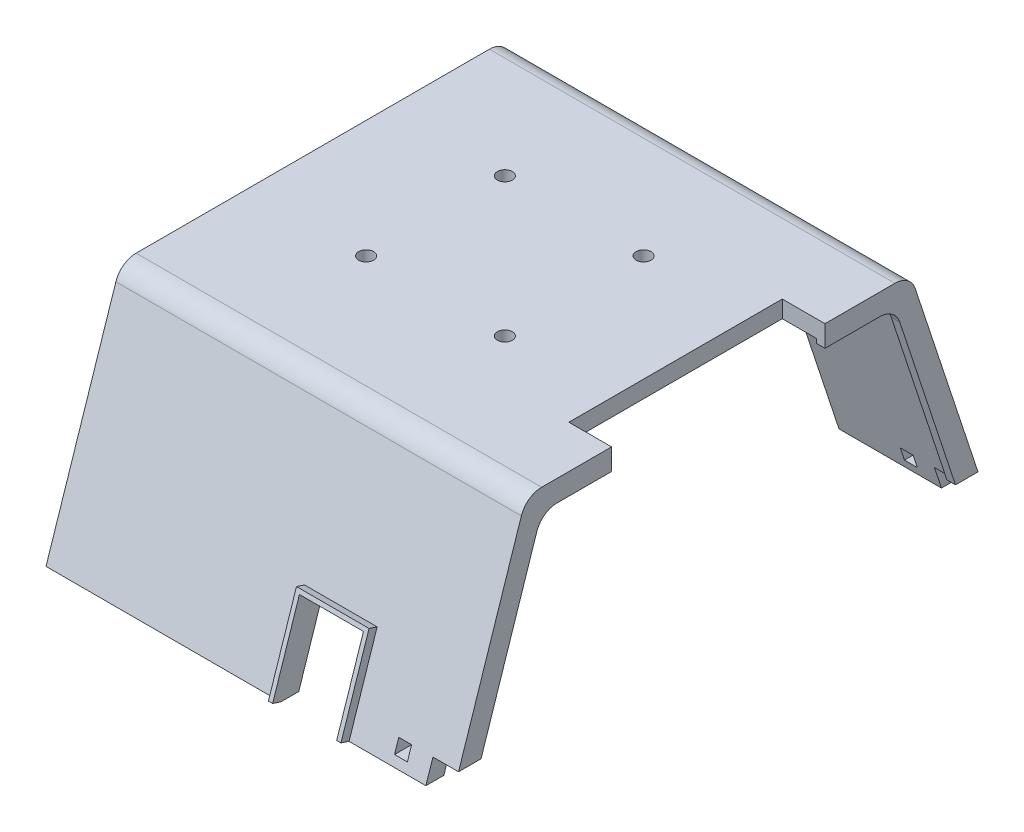
SolidWorks part; units mm, degrees
ref_plane "前视基准面" through (0, 0, 0) normal (0, 0, 1) x (1, 0, 0)
ref_plane "上视基准面" through (0, 0, 0) normal (0, 1, 0) x (1, 0, 0)
ref_plane "右视基准面" through (0, 0, 0) normal (1, 0, 0) x (0, 0, -1)
sketch "草图1" plane through (0, 0, 0) normal (1, 0, 0) x (0, 0, -1)
  line L0 (-62.5, 0) -> (-45, 53)
  line L1 (52.25, 0) -> (-52.25, 0) construction
  line L2 (-45, 53) -> (45, 53)
  line L3 (45, 53) -> (62.5, 0)
  line L4 (62.5, 0) -> (-62.5, 0)
  line L5 (0, 29.15) -> (0, -29.15) construction
  point P4 (0, 53)
  dimension "D1" = 125
  dimension "D2" = 90
  dimension "D3" = 53
extrude "凸台-拉伸1" add sketch "草图1" along normal blind 95
sketch "草图3" plane through (95, 0, 0) normal (1, 0, 0) x (0, 0, -1)
  line L0 (-60.8491, 5) -> (-47.5, 5)
  line L1 (-45, 53) -> (-62.5, 0) construction
  line L2 (-47.5, 5) -> (-47.5, 0)
  line L3 (52.25, 0) -> (-52.25, 0) construction
  line L4 (-47.5, 0) -> (-62.5, 0)
  line L5 (-62.5, 0) -> (-60.8491, 5)
  line L6 (62.5, 0) -> (60.8491, 5)
  line L7 (62.5, 0) -> (45, 53) construction
  line L8 (60.8491, 5) -> (47.5, 5)
  line L9 (47.5, 5) -> (47.5, 0)
  line L10 (47.5, 0) -> (62.5, 0)
  dimension "D1" = 5
  dimension "D2" = 15
  dimension "D3" = 15
  dimension "D4" = 5
extrude "凸台-拉伸3" add sketch "草图3" along normal blind 20
sketch "草图4" plane through (0, 0, 0) normal (0, 0, 1) x (1, 0, 0)
  line L1 (101.5, 3) -> (108.5, 3)
  line L2 (101.5, 3) -> (101.5, 0)
  line L3 (101.5, 0) -> (108.5, 0)
  line L4 (108.5, 3) -> (108.5, 0)
  line L5 (115, 0) -> (0, 0) construction
  line L6 (115, 5) -> (115, 0) construction
  dimension "D1" = 7
  dimension "D2" = 3
  dimension "D3" = 6.5
extrude "切除-拉伸1" cut sketch "草图4" against normal through all and the other way through all
sketch "草图5" plane through (0, 0, 0) normal (0, -1, 0) x (1, 0, 0)
  line L0 (99, -59) -> (99, -51) construction
  line L1 (97.5, -59) -> (97.5, -51)
  line L2 (100.5, -59) -> (100.5, -51)
  line L3 (111, -59) -> (111, -51) construction
  line L4 (109.5, -59) -> (109.5, -51)
  line L5 (112.5, -59) -> (112.5, -51)
  line L6 (99, 51) -> (99, 59) construction
  line L7 (97.5, 51) -> (97.5, 59)
  line L8 (100.5, 51) -> (100.5, 59)
  line L9 (111, 51) -> (111, 59) construction
  line L10 (109.5, 51) -> (109.5, 59)
  line L11 (112.5, 51) -> (112.5, 59)
  line L12 (101.5, -62.5) -> (101.5, -47.5) construction
  line L13 (101.5, -62.5) -> (0, -62.5) construction
  line L14 (115, -62.5) -> (108.5, -62.5) construction
  line L16 (101.5, 47.5) -> (95, 47.5) construction
  line L17 (115, 47.5) -> (108.5, 47.5) construction
  arc A0 (97.5, -59) -> (100.5, -59) centre (99, -59) ccw
  arc A1 (100.5, -51) -> (97.5, -51) centre (99, -51) ccw
  arc A2 (109.5, -59) -> (112.5, -59) centre (111, -59) ccw
  arc A3 (112.5, -51) -> (109.5, -51) centre (111, -51) ccw
  arc A4 (97.5, 51) -> (100.5, 51) centre (99, 51) ccw
  arc A5 (100.5, 59) -> (97.5, 59) centre (99, 59) ccw
  arc A6 (109.5, 51) -> (112.5, 51) centre (111, 51) ccw
  arc A7 (112.5, 59) -> (109.5, 59) centre (111, 59) ccw
  point P2 (99, -55)
  point P7 (111, -55)
  point P14 (99, 55)
  point P21 (111, 55)
  dimension "D1" = 3
  dimension "D2" = 3
  dimension "D3" = 3
  dimension "D4" = 3
  dimension "D5" = 12
  dimension "D6" = 2.5
  dimension "D7" = 7.5
  dimension "D8" = 7.5
  dimension "D9" = 8
  dimension "D10" = 8
  dimension "D11" = 8
  dimension "D12" = 8
  dimension "D13" = 12
  dimension "D14" = 7.5
  dimension "D15" = 7.5
extrude "切除-拉伸2" cut sketch "草图5" against normal through all
shell "抽壳1" thickness 2 removed face at (99, 0, 55)
sketch "草图6" plane through (95, 0, 0) normal (1, 0, 0) x (0, 0, -1)
  line L0 (-37.7709, 48) -> (37.7709, 48)
  line L1 (42.5187, 44.5677) -> (55.5835, 5)
  line L2 (60.8491, 5) -> (47.5, 5) construction
  line L3 (-42.5187, 44.5677) -> (-55.5835, 5)
  line L4 (-47.5, 5) -> (-60.8491, 5) construction
  line L5 (-47.5, 5) -> (-60.8491, 5) construction
  line L6 (-45, 53) -> (-60.8491, 5) construction
  line L7 (60.8491, 5) -> (45, 53) construction
  line L8 (45, 53) -> (-45, 53) construction
  line L9 (-55.5835, 5) -> (-47.5, 5)
  line L10 (-47.5, 5) -> (-47.5, 0)
  line L11 (52.25, 0) -> (-52.25, 0) construction
  line L12 (-47.5, 0) -> (-47.5, 5) construction
  line L13 (47.5, 5) -> (55.5835, 5)
  line L14 (47.5, 5) -> (47.5, 0)
  line L15 (47.5, 5) -> (47.5, 0) construction
  line L16 (-47.5, 0) -> (47.5, 0)
  arc A2 (37.7709, 48) -> (42.5187, 44.5677) centre (37.7709, 43) cw
  arc A3 (-37.7709, 48) -> (-42.5187, 44.5677) centre (-37.7709, 43) ccw
  point P30 (55.5835, 5)
  point P33 (-55.5835, 5)
  dimension "D5" = 5
  dimension "D1" = 5
  dimension "D2" = 5
  dimension "D3" = 5
extrude "切除-拉伸3" cut sketch "草图6" against normal blind 3
sketch "草图7" plane through (0, 53, 0) normal (0, 1, 0) x (1, 0, 0)
  line L0 (95, -25) -> (85, -25)
  line L1 (95, 45) -> (95, -45) construction
  line L2 (85, -25) -> (85, 25)
  line L3 (85, 25) -> (95, 25)
  line L4 (95, -25) -> (95, 25)
  line L6 (27.5, -15) -> (60, -15) construction
  line L7 (27.5, -15) -> (27.5, 17.5) construction
  line L8 (27.5, 17.5) -> (60, 17.5) construction
  line L9 (60, -15) -> (60, 17.5) construction
  line L11 (-29.15, 0) -> (29.15, 0) construction
  circle A0 centre (60, -15) radius 1.75
  circle A1 centre (60, 17.5) radius 1.75
  circle A2 centre (27.5, 17.5) radius 1.75
  circle A3 centre (27.5, -15) radius 1.75
  dimension "D6" = 3.5
  dimension "D7" = 3.5
  dimension "D8" = 3.5
  dimension "D9" = 3.5
  dimension "D1" = 10
  dimension "D2" = 25
  dimension "D3" = 25
  dimension "D4" = 32.5
  dimension "D5" = 32.5
  dimension "D10" = 15
  dimension "D11" = 35
extrude "切除-拉伸4" cut sketch "草图7" against normal through all
sketch "草图9" plane through (0, 18.6081, 56.3558) normal (0, 0.3135, 0.9496) x (1, 0, 0)
  line L0 (55, -19.5962) -> (55, 0.4038)
  line L1 (101.5, -19.5962) -> (0, -19.5962) construction
  line L2 (55, 0.4038) -> (70, 0.4038)
  line L3 (70, 0.4038) -> (70, -19.5962)
  line L4 (70, -19.5962) -> (55, -19.5962)
  line L5 (115, -14.3307) -> (115, -19.5962) construction
  dimension "D1" = 60
  dimension "D2" = 15
  dimension "D3" = 20
extrude "切除-拉伸5" cut sketch "草图9" against normal blind 3 contours L3 L2 L0 L4 region at (62.5, 9.4958, 59.3646)
sketch "草图10" plane through (0, 18.6081, 56.3558) normal (0, 0.3135, 0.9496) x (1, 0, 0)
  line L12 (55, -19.5962) -> (54, -19.5962)
  line L13 (55, -19.5962) -> (0, -19.5962) construction
  line L14 (54, -19.5962) -> (54, 1.4038)
  line L15 (54, 1.4038) -> (71, 1.4038)
  line L16 (71, 1.4038) -> (71, -19.5962)
  line L17 (101.5, -19.5962) -> (70, -19.5962) construction
  line L18 (71, -19.5962) -> (70, -19.5962)
  line L19 (70, -19.5962) -> (70, 0.4038)
  line L20 (70, 0.4038) -> (55, 0.4038)
  line L21 (55, 0.4038) -> (55, -19.5962)
  dimension "D1" = 1
  dimension "D2" = 1
  dimension "D3" = 1
extrude "凸台-拉伸4" add sketch "草图10" along normal blind 2
ref_plane "基准面1" through (0, 0, -80) normal (0, 0, 1) x (1, 0, 0)
sketch "草图11" plane through (0, 18.6081, -56.3558) normal (0, 0.3135, -0.9496) x (-1, 0, 0)
  line L0 (-67, -19.5962) -> (-67, 10.4038)
  line L1 (-101.5, -19.5962) -> (0, -19.5962) construction
  line L2 (-67, 10.4038) -> (-23, 10.4038)
  line L3 (-23, 10.4038) -> (-23, -19.5962)
  line L4 (-23, -19.5962) -> (-25, -19.5962)
  line L5 (-25, -19.5962) -> (-25, 8.4038)
  line L6 (-25, 8.4038) -> (-65, 8.4038)
  line L7 (-65, 8.4038) -> (-65, -19.5962)
  line L8 (-65, -19.5962) -> (-67, -19.5962)
  line L9 (0, 29.15) -> (0, -29.15) construction
  dimension "D1" = 2
  dimension "D2" = 2
  dimension "D3" = 2
  dimension "D4" = 40
  dimension "D5" = 25
  dimension "D6" = 30
extrude "凸台-拉伸6" add sketch "草图11" along normal blind 2 contours L7 L8 L0 L2 L3 L4 L5 L6
sketch "草图13" plane through (0, 18.6081, -56.3558) normal (0, 0.3135, -0.9496) x (-1, 0, 0)
  line L4 (-65, -19.5962) -> (-25, -19.5962)
  line L5 (-25, -19.5962) -> (-25, 8.4038)
  line L6 (-25, 8.4038) -> (-65, 8.4038)
  line L7 (-65, 8.4038) -> (-65, -19.5962)
  line L8 (-65, -19.5962) -> (-25, -19.5962)
  line L9 (-25, -19.5962) -> (-25, 8.4038)
  line L10 (-25, 8.4038) -> (-65, 8.4038)
  line L11 (-65, 8.4038) -> (-65, -19.5962)
  dimension "D1" = 0
extrude "切除-拉伸6" cut sketch "草图13" against normal blind 2
sketch "草图14" plane through (0, 0, 0) normal (-1, 0, 0) x (0, 0, 1)
  line L0 (-41.3854, 48) -> (41.3854, 48)
  line L1 (41.3854, 48) -> (57.2345, 0)
  line L8 (-57.2345, 0) -> (-41.3854, 48)
  line L9 (45, 53) -> (62.5, 0) construction
  line L10 (-62.5, 0) -> (-45, 53) construction
  line L11 (-45, 53) -> (45, 53) construction
  line L14 (52.25, 0) -> (-52.25, 0) construction
  line L16 (57.2345, 0) -> (-57.2345, 0)
  dimension "D1" = 5
  dimension "D2" = 5
  dimension "D3" = 5
extrude "切除-拉伸7" cut sketch "草图14" against normal blind 10
fillet "圆角1" radius 5 2 edges at (47.5, 53, -45) (47.5, 53, 45)
fillet "圆角2" radius 5 2 edges at (1, 48, 41.3854) (1, 48, -41.3854)
sketch "草图15" plane through (0, 17.981, 54.4567) normal (0, -0.3135, -0.9496) x (-1, 0, 0)
  line L15 (-70, -18.9358) -> (-70, 0.4038)
  line L16 (-70, 0.4038) -> (-55, 0.4038)
  line L17 (-55, 0.4038) -> (-55, -18.9358)
  line L20 (-55, -18.9358) -> (-2, -18.9358)
  line L21 (-2, -18.9358) -> (-2, 34.7724)
  line L22 (-2, 34.7724) -> (-93, 34.7724)
  line L23 (-93, 34.7724) -> (-93, -15.7765)
  line L24 (-93, -15.7765) -> (-95.5233, -15.7765)
  line L25 (-95.7895, -18.9358) -> (-70, -18.9358)
  line L28 (-70, -18.9358) -> (-70, 0.4038)
  line L29 (-70, 0.4038) -> (-55, 0.4038)
  line L30 (-55, 0.4038) -> (-55, -18.9358)
  line L33 (-55, -18.9358) -> (-2, -18.9358)
  line L34 (-2, -18.9358) -> (-2, 34.7724)
  line L35 (-2, 34.7724) -> (-93, 34.7724)
  line L36 (-93, 34.7724) -> (-93, -15.7765)
  line L37 (-93, -15.7765) -> (-95.5233, -15.7765)
  line L38 (-95.7895, -18.9358) -> (-70, -18.9358)
  ellipse E1 centre (-99, -14.4904) end of major axis (-99, -25.6533) minor radius 3.5 (-95.7895, -18.9358) -> (-95.5233, -15.7765) ccw
  ellipse E2 centre (-99, -14.4904) end of major axis (-99, -25.6533) minor radius 3.5 (-95.7895, -18.9358) -> (-95.5233, -15.7765) ccw
  dimension "D1" = 0
extrude "凸台-拉伸7" add sketch "草图15" along normal blind 2
sketch "草图16" plane through (0, 17.981, -54.4567) normal (0, -0.3135, 0.9496) x (1, 0, 0)
  line L9 (65, 8.4038) -> (65, -18.9358)
  line L10 (65, -18.9358) -> (95.7895, -18.9358)
  line L11 (95.5233, -15.7765) -> (93, -15.7765)
  line L12 (93, -15.7765) -> (93, 34.7724)
  line L13 (93, 34.7724) -> (2, 34.7724)
  line L14 (2, 34.7724) -> (2, -18.9358)
  line L15 (2, -18.9358) -> (25, -18.9358)
  line L16 (25, -18.9358) -> (25, 8.4038)
  line L17 (25, 8.4038) -> (65, 8.4038)
  line L18 (65, 8.4038) -> (65, -18.9358)
  line L19 (65, -18.9358) -> (95.7895, -18.9358)
  line L20 (95.5233, -15.7765) -> (93, -15.7765)
  line L21 (93, -15.7765) -> (93, 34.7724)
  line L22 (93, 34.7724) -> (2, 34.7724)
  line L23 (2, 34.7724) -> (2, -18.9358)
  line L24 (2, -18.9358) -> (25, -18.9358)
  line L25 (25, -18.9358) -> (25, 8.4038)
  line L26 (25, 8.4038) -> (65, 8.4038)
  ellipse E1 centre (99, -14.4904) end of major axis (99, -25.6533) minor radius 3.5 (95.5233, -15.7765) -> (95.7895, -18.9358) ccw
  ellipse E2 centre (99, -14.4904) end of major axis (99, -25.6533) minor radius 3.5 (95.5233, -15.7765) -> (95.7895, -18.9358) ccw
  dimension "D1" = 0
extrude "凸台-拉伸8" add sketch "草图16" along normal blind 2
sketch "草图17" plane through (0, 51, 0) normal (0, -1, 0) x (1, 0, 0)
  line L8 (85, 25) -> (93, 25)
  line L9 (93, 25) -> (93, 43.5542)
  line L10 (93, 43.5542) -> (2, 43.5542)
  line L11 (2, 43.5542) -> (2, -43.5542)
  line L12 (2, -43.5542) -> (93, -43.5542)
  line L13 (93, -43.5542) -> (93, -25)
  line L14 (93, -25) -> (85, -25)
  line L15 (85, -25) -> (85, 25)
  line L16 (85, 25) -> (93, 25)
  line L17 (93, 25) -> (93, 43.5542)
  line L18 (93, 43.5542) -> (2, 43.5542)
  line L19 (2, 43.5542) -> (2, -43.5542)
  line L20 (2, -43.5542) -> (93, -43.5542)
  line L21 (93, -43.5542) -> (93, -25)
  line L22 (93, -25) -> (85, -25)
  line L23 (85, -25) -> (85, 25)
  circle A0 centre (60, -17.5) radius 1.75 construction
  circle A1 centre (27.5, -17.5) radius 1.75 construction
  circle A2 centre (60, 15) radius 1.75 construction
  circle A3 centre (27.5, 15) radius 1.75 construction
  circle A4 centre (60, -17.5) radius 1.75
  circle A5 centre (27.5, -17.5) radius 1.75
  circle A6 centre (60, 15) radius 1.75
  circle A7 centre (27.5, 15) radius 1.75
  dimension "D1" = 0
extrude "凸台-拉伸9" add sketch "草图17" along normal blind 2
sketch "草图18" plane through (0, 0, 0) normal (0, 1, 0) x (1, 0, 0)
  line L1 (118.2231, -67.1697) -> (-1.9092, -67.1697)
  line L2 (118.2231, -67.1697) -> (118.2231, 67.416)
  line L3 (118.2231, 67.416) -> (-1.9092, 67.416)
  line L4 (-1.9092, -67.1697) -> (-1.9092, 67.416)
extrude "切除-拉伸8" cut sketch "草图18" against normal blind 2
sketch "草图20" plane through (95, 0, 0) normal (1, 0, 0) x (0, 0, -1)
  line L1 (-84.5987, 74.8279) -> (90.9423, 74.8279)
  line L2 (-84.5987, 74.8279) -> (-84.5987, -22.4781)
  line L3 (-84.5987, -22.4781) -> (90.9423, -22.4781)
  line L4 (90.9423, 74.8279) -> (90.9423, -22.4781)
extrude "切除-拉伸9" cut sketch "草图20" along normal blind 39
sketch "草图21" plane through (95, 0, 0) normal (1, 0, 0) x (0, 0, -1)
  line L0 (-43.8612, 40.5019) -> (-57.2345, 0)
  line L1 (-42.5187, 44.5677) -> (-55.5835, 5) construction
  line L2 (52.25, 0) -> (-52.25, 0) construction
  line L3 (-57.2345, 0) -> (57.2345, 0)
  line L4 (57.2345, 0) -> (43.8612, 40.5019)
  line L5 (55.5835, 5) -> (42.5187, 44.5677) construction
  line L6 (43.8612, 40.5019) -> (-43.8612, 40.5019)
extrude "切除-拉伸10" cut sketch "草图21" against normal blind 39
sketch "草图23" plane through (0, 0, -80) normal (0, 0, 1) x (1, 0, 0)
  line L0 (95, 5) -> (89, 5)
  line L1 (95, 0) -> (95, 49.5677) construction
  line L2 (89, 5) -> (89, 0)
  line L3 (52.25, 0) -> (-52.25, 0) construction
  line L4 (89, 0) -> (95, 0)
  line L5 (95, 0) -> (95, 5)
  line L15 (84, 5) -> (81, 5)
  line L16 (84, 5) -> (84, 2)
  line L17 (84, 2) -> (81, 2)
  line L18 (81, 5) -> (81, 2)
  dimension "D1" = 5
  dimension "D2" = 6
  dimension "D3" = 3
  dimension "D4" = 3
  dimension "D5" = 5
extrude "切除-拉伸11" cut sketch "草图23" along normal through all
sketch "草图24" [suppressed] plane through (0, 5, 0) normal (0, 1, 0) x (1, 0, 0)
  line L0 (95, -60.8491) -> (89, -60.8491)
  line L1 (89, -60.8491) -> (89, -47.5)
  line L2 (89, -47.5) -> (95, -47.5)
  line L3 (95, -46.1333) -> (95, -60.8491) construction
  line L4 (115, -47.5) -> (93, -47.5) construction
  line L5 (95, -60.8491) -> (95, -47.5)
  dimension "D1" = 6
